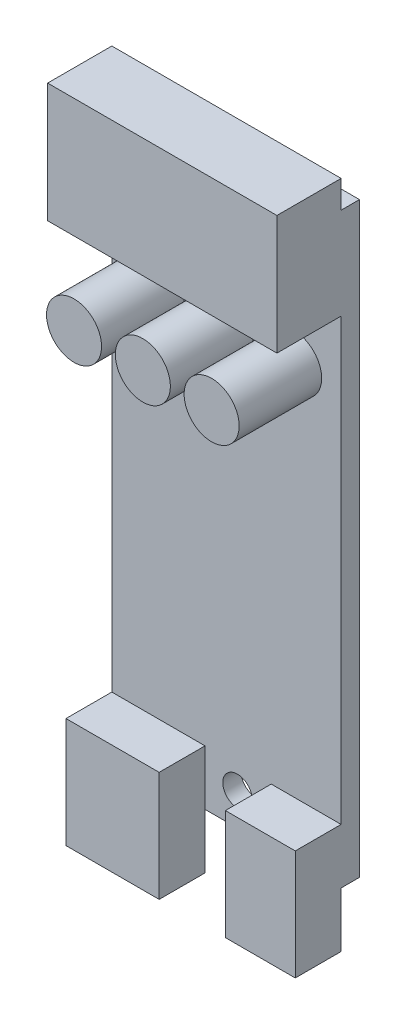
SolidWorks part; units mm, degrees
ref_plane "Front Plane" through (0, 0, 0) normal (0, 0, 1) x (1, 0, 0)
ref_plane "Top Plane" through (0, 0, 0) normal (0, 1, 0) x (1, 0, 0)
ref_plane "Right Plane" through (0, 0, 0) normal (1, 0, 0) x (0, 0, -1)
ref_plane "Plane1" through (0, 0, 0) normal (0, 0, -1) x (-1, 0, 0)
sketch "Sketch1" plane through (0, 0, 0) normal (0, 0, -1) x (-1, 0, 0)
  line L0 (0, 0) -> (0, 67)
  line L1 (0, 67) -> (-25, 67)
  line L2 (-25, 67) -> (-25, 0)
  line L3 (-25, 0) -> (0, 0)
extrude "Boss-Extrude1" add sketch "Sketch1" against normal blind 9
sketch "Sketch2" plane through (0, 0, 0) normal (-1, 0, 0) x (0, 0, 1)
  line L0 (0, 67) -> (0, 64)
  line L1 (0, 64) -> (2, 64)
  line L2 (2, 64) -> (2, 67)
  line L3 (2, 67) -> (0, 67)
extrude "Cut-Extrude1" cut sketch "Sketch2" against normal through all
sketch "Sketch3" plane through (0, 0, 0) normal (-1, 0, 0) x (0, 0, 1)
  line L0 (9, 54) -> (2, 54)
  line L1 (2, 54) -> (2, 0)
  line L2 (2, 0) -> (9, 0)
  line L3 (9, 0) -> (9, 54)
extrude "Cut-Extrude2" cut sketch "Sketch3" against normal through all
ref_plane "Plane2" through (0, 0, 0) normal (-1, 0, 0) x (0, -1, 0)
sketch "Sketch4" plane through (0, 0, 0) normal (-1, 0, 0) x (0, -1, 0)
  line L0 (-6, 2) -> (0, 2)
  line L1 (0, 2) -> (6, 2)
  line L2 (6, 2) -> (6, 7)
  line L3 (6, 7) -> (-6, 7)
  line L4 (-6, 7) -> (-6, 2)
extrude "Boss-Extrude2" add sketch "Sketch4" against normal blind 10.16
ref_plane "Plane3" through (25, 0, 0) normal (1, 0, 0) x (0, 0, -1)
sketch "Sketch5" plane through (25, 0, 0) normal (1, 0, 0) x (0, 0, -1)
  line L0 (-2, 0) -> (-2, 6)
  line L1 (-2, 6) -> (-7, 6)
  line L2 (-7, 6) -> (-7, -6)
  line L3 (-7, -6) -> (-2, -6)
  line L4 (-2, -6) -> (-2, 0)
extrude "Boss-Extrude3" add sketch "Sketch5" against normal blind 7.62
ref_plane "Plane4" through (0, 47.0647, 0) normal (0, -1, 0) x (1, 0, 0)
sketch "Sketch6" plane through (0, 47.0647, 0) normal (0, -1, 0) x (1, 0, 0)
  line L0 (22.8803, 11) -> (19.8803, 11)
  line L1 (19.8803, 11) -> (19.8803, 2)
  line L2 (19.8803, 2) -> (22.8803, 2)
  line L3 (22.8803, 2) -> (22.8803, 11)
  line L4 (19.8803, 11) -> (19.8803, 2) construction
revolve "Revolve1" add sketch "Sketch6" angle 360 about L4 reverse direction yes
sketch "Sketch7" plane through (0, 47.0647, 0) normal (0, -1, 0) x (1, 0, 0)
  line L0 (15.3803, 11) -> (12.3803, 11)
  line L1 (12.3803, 11) -> (12.3803, 2)
  line L2 (12.3803, 2) -> (15.3803, 2)
  line L3 (15.3803, 2) -> (15.3803, 11)
  line L4 (12.3803, 11) -> (12.3803, 2) construction
revolve "Revolve2" add sketch "Sketch7" angle 360 about L4 reverse direction yes
sketch "Sketch8" plane through (0, 47.0647, 0) normal (0, -1, 0) x (1, 0, 0)
  line L0 (7.8803, 11) -> (4.8803, 11)
  line L1 (4.8803, 11) -> (4.8803, 2)
  line L2 (4.8803, 2) -> (7.8803, 2)
  line L3 (7.8803, 2) -> (7.8803, 11)
  line L4 (4.8803, 11) -> (4.8803, 2) construction
revolve "Revolve3" add sketch "Sketch8" angle 360 about L4 reverse direction yes
hole_wizard "Ø3.2 (3.2) Diameter Hole1" positions "Sketch10" profile "Sketch9" hole size "Ø3.2" standard "ANSI Metric"
sketch "Sketch10" plane through (0, 0, 0) normal (0, 0, -1) x (-1, 0, 0)
  point P0 (-15.2, 40.7)
  point P1 (-13.7, 3.5)
sketch "Sketch9" plane through (15.2, 40.7, 0) normal (1, 0, 0) x (0, 1, 0)
  line L0 (0, 0) -> (0, 11)
  line L1 (0, 11) -> (1.6, 11)
  line L2 (1.6, 11) -> (1.6, 0)
  line L5 (1.6, 0) -> (0, 0)
  line L11 (0, -6.35) -> (0, 107.95) construction
  dimension "Thru Hole Dia." = 3.2
  dimension "Thru Hole Depth" = 11
